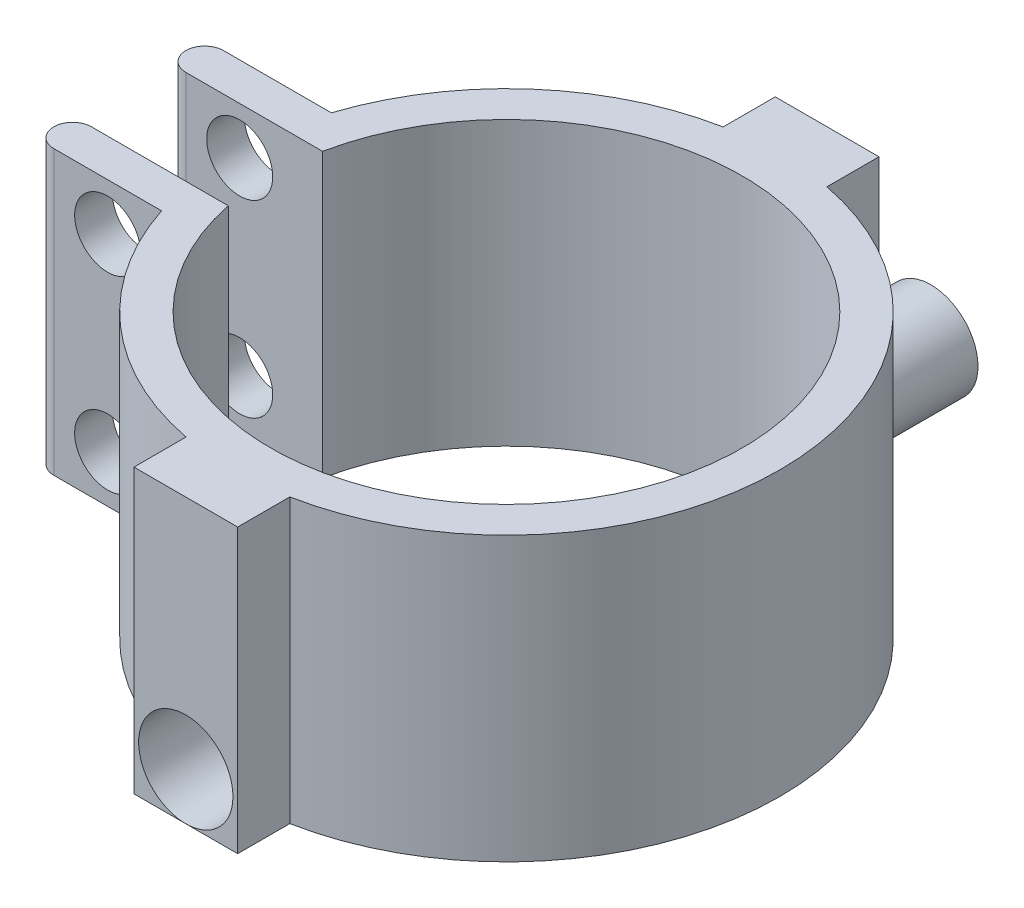
SolidWorks part; units mm, degrees
ref_plane "Front Plane" through (0, 0, 0) normal (0, 0, 1) x (1, 0, 0)
ref_plane "Top Plane" through (0, 0, 0) normal (0, 1, 0) x (1, 0, 0)
ref_plane "Right Plane" through (0, 0, 0) normal (1, 0, 0) x (0, 0, -1)
sketch "Sketch1" plane through (0, 0, 0) normal (0, 1, 0) x (1, 0, 0)
  line L0 (-12.5, -17.5) -> (-12.5, 17.5) construction
  line L1 (-30, -17.5) -> (30, -17.5)
  line L2 (-30, -17.5) -> (-30, 17.5)
  line L3 (-30, 17.5) -> (30, 17.5)
  line L4 (30, -17.5) -> (30, 17.5)
  line L5 (-30, -17.5) -> (30, 17.5) construction
  line L6 (-30, 17.5) -> (30, -17.5) construction
  line L7 (-12.2474, -2.5) -> (-12.5, -2.5)
  line L8 (-12.2474, 2.5) -> (-12.5, 2.5)
  line L9 (-12.5, -2.5) -> (-19.5, -2.5)
  line L10 (-12.5, 2.5) -> (-19.5, 2.5)
  line L11 (-13.784, 4.5) -> (-19.5, 4.5)
  line L12 (-13.784, 4.5) -> (-13.784, 4.5)
  line L13 (-13.784, -4.5) -> (-13.784, -4.5)
  line L14 (-13.784, -4.5) -> (-19.5, -4.5)
  line L15 (-30, -14.5) -> (30, -14.5) construction
  line L16 (-2.75, -14.2368) -> (-2.75, -14.5)
  line L17 (2.75, -14.5) -> (2.75, -14.2368)
  line L18 (0, 0) -> (10.0696, 0) construction
  line L19 (-2.75, -14.5) -> (2.75, -14.5) construction
  line L20 (-2.75, -14.5) -> (-2.75, -17)
  line L21 (-2.75, -17) -> (2.75, -17)
  line L22 (2.75, -14.5) -> (2.75, -17)
  line L23 (2.75, 14.5) -> (2.75, 17)
  line L24 (-2.75, 17) -> (2.75, 17)
  line L25 (-2.75, 14.5) -> (-2.75, 17)
  line L26 (-2.75, 14.5) -> (2.75, 14.5) construction
  line L27 (2.75, 14.5) -> (2.75, 14.2368)
  line L28 (-2.75, 14.2368) -> (-2.75, 14.5)
  circle A0 centre (0, 0) radius 12.5 construction
  arc A1 (-12.2474, 2.5) -> (-12.2474, -2.5) centre (0, 0) cw
  arc A2 (-13.784, 4.5) -> (-13.784, -4.5) centre (0, 0) cw
  arc A3 (-19.5, 2.5) -> (-19.5, 4.5) centre (-19.5, 3.5) cw
  arc A4 (-19.5, -2.5) -> (-19.5, -4.5) centre (-19.5, -3.5) ccw
  point P0 (0, 0)
  point P15 (-12.5, 0)
  point P32 (0, 14.5)
  point P40 (0, -14.5)
  dimension "D3" = 25
  dimension "D1" = 60
  dimension "D2" = 35
  dimension "D4" = 7
  dimension "D6" = 5
  dimension "D7" = 5.5
  dimension "D8" = 0.5
  dimension "D5" = 2
extrude "Boss-Extrude1" add sketch "Sketch1" along normal mid plane 5.001 contours L9 A4 L14 A2 L11 A3 L10 L8 A1 L7 | L17 A2 L16 L20 L21 L22 | L28 A2 L27 L23 L24 L25 region at (12.9545, 0, 0) region at (0, 0, 15.7051) region at (0, 0, -15.7051)
sketch "Sketch6" plane through (0, 2.5005, 0) normal (0, 1, 0) x (1, 0, 0)
  line L12 (-12.2474, -2.5) -> (-19.5, -2.5)
  line L13 (-19.5, -4.5) -> (-13.784, -4.5)
  line L14 (-2.75, -14.2368) -> (-2.75, -17)
  line L15 (-2.75, -17) -> (2.75, -17)
  line L17 (2.75, -17) -> (2.75, -14.2368)
  line L18 (2.75, 14.2368) -> (2.75, 17)
  line L19 (2.75, 17) -> (-2.75, 17)
  line L21 (-2.75, 17) -> (-2.75, 14.2368)
  line L22 (-13.784, 4.5) -> (-19.5, 4.5)
  line L23 (-19.5, 2.5) -> (-12.2474, 2.5)
  line L24 (-12.2474, -2.5) -> (-19.5, -2.5)
  line L25 (-19.5, -4.5) -> (-13.784, -4.5)
  line L26 (-2.75, -14.2368) -> (-2.75, -17)
  line L27 (-2.75, -17) -> (2.75, -17)
  line L29 (2.75, -17) -> (2.75, -14.2368)
  line L30 (2.75, 14.2368) -> (2.75, 17)
  line L31 (2.75, 17) -> (-2.75, 17)
  line L33 (-2.75, 17) -> (-2.75, 14.2368)
  line L34 (-13.784, 4.5) -> (-19.5, 4.5)
  line L35 (-19.5, 2.5) -> (-12.2474, 2.5)
  arc A6 (-19.5, -2.5) -> (-19.5, -4.5) centre (-19.5, -3.5) ccw
  arc A7 (-13.784, -4.5) -> (-2.75, -14.2368) centre (0, 0) ccw
  arc A8 (2.75, -14.2368) -> (2.75, 14.2368) centre (0, 0) ccw
  arc A9 (-2.75, 14.2368) -> (-13.784, 4.5) centre (0, 0) ccw
  arc A10 (-19.5, 4.5) -> (-19.5, 2.5) centre (-19.5, 3.5) ccw
  arc A11 (-12.2474, -2.5) -> (-12.2474, 2.5) centre (0, 0) ccw
  arc A12 (-19.5, -2.5) -> (-19.5, -4.5) centre (-19.5, -3.5) ccw
  arc A13 (-13.784, -4.5) -> (-2.75, -14.2368) centre (0, 0) ccw
  arc A14 (2.75, -14.2368) -> (2.75, 14.2368) centre (0, 0) ccw
  arc A15 (-2.75, 14.2368) -> (-13.784, 4.5) centre (0, 0) ccw
  arc A16 (-19.5, 4.5) -> (-19.5, 2.5) centre (-19.5, 3.5) ccw
  arc A17 (-12.2474, -2.5) -> (-12.2474, 2.5) centre (0, 0) ccw
  dimension "D1" = 0
extrude "Boss-Extrude3" add sketch "Sketch6" along normal blind 10
sketch "Sketch3" plane through (0, 0, 4.5) normal (0, 0, 1) x (1, 0, 0)
  line L2 (-13.784, -2.5005) -> (-19.5, -2.5005) construction
  line L3 (-16.642, 12.5005) -> (-16.642, 10.0005) construction
  line L4 (-19.5, 12.5005) -> (-13.784, 12.5005) construction
  circle A0 centre (-16.642, 0) radius 1.75
  circle A1 centre (-16.642, 10.0005) radius 1.75
  point P0 (-16.642, -2.5005)
  dimension "D1" = 3.5
  dimension "D2" = 2.5
extrude "Cut-Extrude1" cut sketch "Sketch3" against normal up to surface (9 mm away) up to face at (-16.642, 5, -4.5)
sketch "Sketch4" plane through (0, 0, -17) normal (0, 0, 1) x (1, 0, 0)
  circle A1 centre (0, 0) radius 2.5
  dimension "D1" = 5
extrude "Boss-Extrude2" add sketch "Sketch4" against normal blind 5.5
sketch "Sketch7" plane through (0, 0, 17) normal (0, 0, 1) x (1, 0, 0)
  circle A0 centre (0, 0) radius 2.5
  dimension "D1" = 5
extrude "Cut-Extrude10" cut sketch "Sketch7" against normal up to next
equation "\"a\"= 1"
equation "\"b\"= 1"
equation "\"c\"= 1"
equation "\"d\"= 1"
equation "\"e\"= 1"
equation "\"x\"= 1"
equation "\"y\"= 1"
equation "\"z\"= 1"
